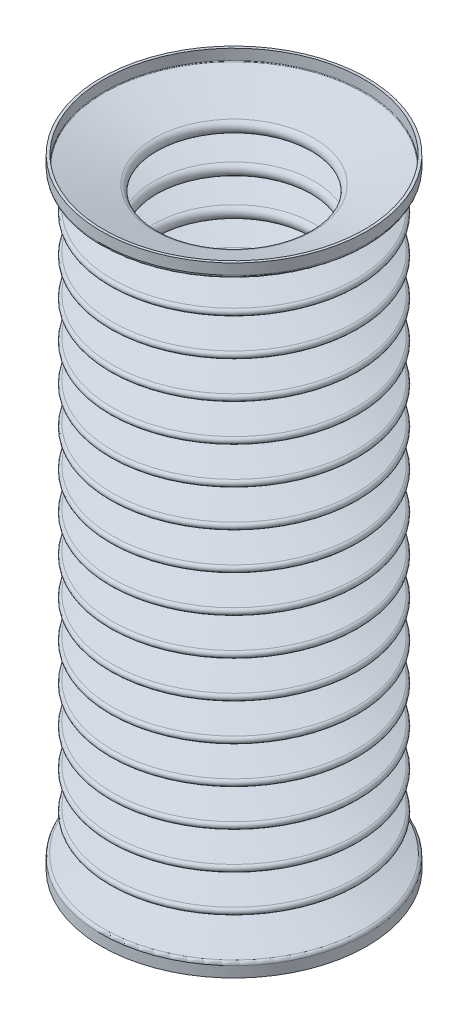
SolidWorks part; units mm, degrees
ref_plane "Front Plane" through (0, 0, 0) normal (0, 0, 1) x (1, 0, 0)
ref_plane "Top Plane" through (0, 0, 0) normal (0, 1, 0) x (1, 0, 0)
ref_plane "Right Plane" through (0, 0, 0) normal (1, 0, 0) x (0, 0, -1)
sketch "Sketch1" plane through (0, 0, 0) normal (0, 0, 1) x (1, 0, 0)
  line L0 (0, 0) -> (0, 279.4)
  line L1 (0, 0) -> (59.944, 0)
  line L2 (59.944, 0) -> (59.944, 4.8283)
  line L3 (31.496, 0) -> (31.496, 304.8) construction
  line L4 (58.8496, 6.2905) -> (36.4727, 12.865)
  line L5 (36.4727, 15.7894) -> (54.9673, 21.2232)
  line L6 (31.496, 14.3272) -> (59.944, 14.3272) construction
  line L7 (59.944, 5.969) -> (59.944, 22.6854) construction
  line L8 (54.9673, 24.1476) -> (36.4727, 29.5814)
  line L9 (36.4727, 32.5058) -> (54.9673, 37.9396)
  line L10 (54.9673, 40.8639) -> (36.4727, 46.2977)
  line L11 (36.4727, 49.2221) -> (54.9673, 54.6559)
  line L12 (54.9673, 57.5803) -> (36.4727, 63.0141)
  line L13 (36.4727, 65.9385) -> (54.9673, 71.3723)
  line L14 (54.9673, 74.2967) -> (36.4727, 79.7305)
  line L15 (36.4727, 82.6549) -> (54.9673, 88.0887)
  line L16 (54.9673, 91.0131) -> (36.4727, 96.4469)
  line L17 (36.4727, 99.3713) -> (54.9673, 104.8051)
  line L18 (54.9673, 107.7294) -> (36.4727, 113.1632)
  line L19 (36.4727, 116.0876) -> (54.9673, 121.5214)
  line L20 (54.9673, 124.4458) -> (36.4727, 129.8796)
  line L21 (36.4727, 132.804) -> (54.9673, 138.2378)
  line L22 (54.9673, 141.1622) -> (36.4727, 146.596)
  line L23 (36.4727, 149.5204) -> (54.9673, 154.9542)
  line L24 (54.9673, 157.8786) -> (36.4727, 163.3124)
  line L25 (36.4727, 166.2368) -> (54.9673, 171.6706)
  line L26 (54.9673, 174.5949) -> (36.4727, 180.0287)
  line L27 (36.4727, 182.9531) -> (54.9673, 188.3869)
  line L28 (54.9673, 191.3113) -> (36.4727, 196.7451)
  line L29 (36.4727, 199.6695) -> (54.9673, 205.1033)
  line L30 (54.9673, 208.0277) -> (36.4727, 213.4615)
  line L31 (36.4727, 216.3859) -> (54.9673, 221.8197)
  line L32 (54.9673, 224.7441) -> (36.4727, 230.1779)
  line L33 (36.4727, 233.1023) -> (54.9673, 238.5361)
  line L34 (54.9673, 241.4604) -> (36.4727, 246.8942)
  line L35 (36.4727, 249.8186) -> (54.9673, 255.2524)
  line L36 (54.9673, 258.1768) -> (36.4727, 263.6106)
  line L37 (36.4727, 266.535) -> (58.8496, 273.1095)
  line L38 (0, 139.7) -> (155.8281, 139.7) construction
  line L39 (59.944, 279.4) -> (59.944, 274.5717)
  line L40 (0, 279.4) -> (59.944, 279.4)
  arc A0 (59.944, 4.8283) -> (58.8496, 6.2905) centre (58.42, 4.8283) ccw
  arc A1 (59.944, 274.5717) -> (58.8496, 273.1095) centre (58.42, 274.5717) cw
  arc A2 (36.4727, 263.6106) -> (36.4727, 266.535) centre (36.9023, 265.0728) cw
  arc A3 (54.9673, 255.2524) -> (54.9673, 258.1768) centre (54.5377, 256.7146) ccw
  arc A4 (36.4727, 246.8942) -> (36.4727, 249.8186) centre (36.9023, 248.3564) cw
  arc A5 (54.9673, 238.5361) -> (54.9673, 241.4604) centre (54.5377, 239.9983) ccw
  arc A6 (36.4727, 230.1779) -> (36.4727, 233.1023) centre (36.9023, 231.6401) cw
  arc A7 (54.9673, 221.8197) -> (54.9673, 224.7441) centre (54.5377, 223.2819) ccw
  arc A8 (36.4727, 213.4615) -> (36.4727, 216.3859) centre (36.9023, 214.9237) cw
  arc A9 (54.9673, 205.1033) -> (54.9673, 208.0277) centre (54.5377, 206.5655) ccw
  arc A10 (36.4727, 196.7451) -> (36.4727, 199.6695) centre (36.9023, 198.2073) cw
  arc A11 (54.9673, 188.3869) -> (54.9673, 191.3113) centre (54.5377, 189.8491) ccw
  arc A12 (36.4727, 180.0287) -> (36.4727, 182.9531) centre (36.9023, 181.4909) cw
  arc A13 (54.9673, 171.6706) -> (54.9673, 174.5949) centre (54.5377, 173.1328) ccw
  arc A14 (36.4727, 163.3124) -> (36.4727, 166.2368) centre (36.9023, 164.7746) cw
  arc A15 (54.9673, 154.9542) -> (54.9673, 157.8786) centre (54.5377, 156.4164) ccw
  arc A16 (36.4727, 146.596) -> (36.4727, 149.5204) centre (36.9023, 148.0582) cw
  arc A17 (54.9673, 138.2378) -> (54.9673, 141.1622) centre (54.5377, 139.7) ccw
  arc A18 (36.4727, 129.8796) -> (36.4727, 132.804) centre (36.9023, 131.3418) cw
  arc A19 (54.9673, 121.5214) -> (54.9673, 124.4458) centre (54.5377, 122.9836) ccw
  arc A20 (36.4727, 113.1632) -> (36.4727, 116.0876) centre (36.9023, 114.6254) cw
  arc A21 (54.9673, 104.8051) -> (54.9673, 107.7294) centre (54.5377, 106.2673) ccw
  arc A22 (36.4727, 96.4469) -> (36.4727, 99.3713) centre (36.9023, 97.9091) cw
  arc A23 (54.9673, 88.0887) -> (54.9673, 91.0131) centre (54.5377, 89.5509) ccw
  arc A24 (36.4727, 79.7305) -> (36.4727, 82.6549) centre (36.9023, 81.1927) cw
  arc A25 (54.9673, 71.3723) -> (54.9673, 74.2967) centre (54.5377, 72.8345) ccw
  arc A26 (36.4727, 63.0141) -> (36.4727, 65.9385) centre (36.9023, 64.4763) cw
  arc A27 (54.9673, 54.6559) -> (54.9673, 57.5803) centre (54.5377, 56.1181) ccw
  arc A28 (36.4727, 46.2977) -> (36.4727, 49.2221) centre (36.9023, 47.7599) cw
  arc A29 (54.9673, 37.9396) -> (54.9673, 40.8639) centre (54.5377, 39.4018) ccw
  arc A30 (36.4727, 29.5814) -> (36.4727, 32.5058) centre (36.9023, 31.0436) cw
  arc A31 (54.9673, 21.2232) -> (54.9673, 24.1476) centre (54.5377, 22.6854) ccw
  arc A32 (36.4727, 12.865) -> (36.4727, 15.7894) centre (36.9023, 14.3272) cw
  point P12 (59.944, 14.3272)
  point P37 (59.944, 273.431)
  dimension "D7" = 1.524
  dimension "D1" = 59.944
  dimension "D2" = 5.969
  dimension "D3" = 279.4
  dimension "D4" = 31.496
  dimension "D6" = 16.7164
  dimension "D5" = 16
revolve "Revolve2" add sketch "Sketch1" angle 360 about L0
shell "Shell1" thickness 1.1938 removed face at (59.944, 0, 0) removed face at (59.944, 279.4, 0)
ref_axis "Axis1" through (0, 320.04, 0) along (0, -1, 0)
